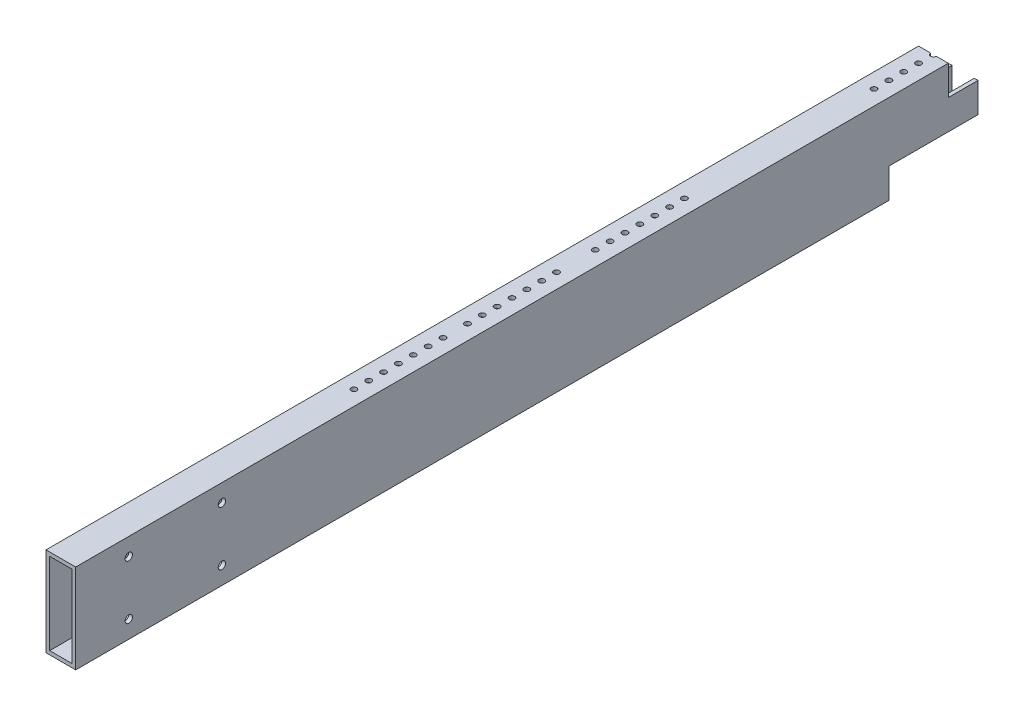
SolidWorks part; units mm, degrees
ref_plane "Front Plane" through (0, 0, 0) normal (0, 0, 1) x (1, 0, 0)
ref_plane "Top Plane" through (0, 0, 0) normal (0, 1, 0) x (1, 0, 0)
ref_plane "Right Plane" through (0, 0, 0) normal (1, 0, 0) x (0, 0, -1)
sketch "Sketch1" plane through (0, 0, 0) normal (0, 0, 1) x (1, 0, 0)
  line L1 (-12.7, -38.1) -> (12.7, -38.1)
  line L2 (-12.7, -38.1) -> (-12.7, 38.1)
  line L3 (-12.7, 38.1) -> (12.7, 38.1)
  line L4 (12.7, -38.1) -> (12.7, 38.1)
  line L5 (-12.7, -38.1) -> (12.7, 38.1) construction
  line L6 (-12.7, 38.1) -> (12.7, -38.1) construction
  point P0 (0, 0)
  dimension "D1" = 25.4
  dimension "D2" = 76.2
extrude "Boss-Extrude1" add sketch "Sketch1" along normal mid plane 771.398
shell "Shell1" thickness 3.175 removed face at (0, 0, -385.699) removed face at (0, 0, 385.699)
sketch "Sketch2" plane through (12.7, 0, 0) normal (1, 0, 0) x (0, 0, -1)
  line L1 (385.699, -38.1) -> (309.499, -38.1)
  line L2 (385.699, -38.1) -> (385.699, -12.7)
  line L3 (385.699, -12.7) -> (309.499, -12.7)
  line L4 (309.499, -38.1) -> (309.499, -12.7)
  dimension "D1" = 25.4
  dimension "D2" = 76.2
extrude "Cut-Extrude1" cut sketch "Sketch2" against normal through all
sketch "Sketch3" plane through (12.7, 0, 0) normal (1, 0, 0) x (0, 0, -1)
  line L1 (385.699, 38.1) -> (360.299, 38.1)
  line L2 (385.699, 38.1) -> (385.699, 12.7)
  line L3 (385.699, 12.7) -> (360.299, 12.7)
  line L4 (360.299, 38.1) -> (360.299, 12.7)
  dimension "D1" = 25.4
extrude "Cut-Extrude2" cut sketch "Sketch3" against normal through all
sketch "Sketch4" plane through (0, 38.1, 0) normal (0, 1, 0) x (1, 0, 0)
  line L0 (-12.7, 360.299) -> (12.7, 360.299) construction
  circle A0 centre (0, 147.3945) radius 2.3812
  circle A1 centre (0, 134.6945) radius 2.3812
  circle A2 centre (0, 121.9945) radius 2.3812
  circle A3 centre (0, 109.2945) radius 2.3812
  circle A4 centre (0, 96.5945) radius 2.3812
  circle A5 centre (0, 83.8945) radius 2.3812
  circle A6 centre (0, 71.1945) radius 2.3812
  circle A7 centre (0, 38.0987) radius 2.3812
  circle A8 centre (0, 25.3987) radius 2.3813
  circle A9 centre (0, 12.6987) radius 2.3813
  circle A10 centre (0, -0.0013) radius 2.3813
  circle A11 centre (0, -12.7013) radius 2.3812
  circle A12 centre (0, -25.4013) radius 2.3812
  circle A13 centre (0, -38.1013) radius 2.3812
  circle A15 centre (0, -58.9932) radius 2.3812
  circle A16 centre (0, -71.6932) radius 2.3812
  circle A17 centre (0, -84.3932) radius 2.3812
  circle A18 centre (0, -97.0932) radius 2.3812
  circle A19 centre (0, -109.7932) radius 2.3812
  circle A20 centre (0, -122.4932) radius 2.3812
  circle A21 centre (0, -135.1932) radius 2.3813
  point P33 (0, 360.299)
  dimension "D1" = 4.7625
  dimension "D3" = 12.7
  dimension "D4" = 12.7
  dimension "D5" = 12.7
  dimension "D6" = 12.7
  dimension "D7" = 12.7
  dimension "D8" = 12.7
  dimension "D9" = 322.2003
  dimension "D10" = 12.7
  dimension "D11" = 12.7
  dimension "D12" = 12.7
  dimension "D13" = 12.7
  dimension "D14" = 12.7
  dimension "D15" = 12.7
  dimension "D16" = 12.7
  dimension "D17" = 419.2922
  dimension "D18" = 12.7
  dimension "D19" = 12.7
  dimension "D20" = 12.7
  dimension "D21" = 12.7
  dimension "D22" = 12.7
  dimension "D2" = 212.9045
extrude "Cut-Extrude3" cut sketch "Sketch4" against normal through all
sketch "Sketch5" plane through (0, 38.1, 0) normal (0, 1, 0) x (1, 0, 0)
  line L0 (-12.7, 360.299) -> (12.7, 360.299) construction
  circle A0 centre (0, 360.299) radius 2.3813
  circle A1 centre (0, 347.599) radius 2.3813
  circle A2 centre (0, 334.899) radius 2.3813
  circle A3 centre (0, 322.199) radius 2.3813
  circle A4 centre (0, 309.499) radius 2.3813
  dimension "D1" = 4.7625
  dimension "D3" = 12.7
  dimension "D4" = 12.7
  dimension "D5" = 12.7
  dimension "D8" = 0
  dimension "D2" = 12.7
extrude "Cut-Extrude4" cut sketch "Sketch5" against normal up to next
sketch "Sketch6" plane through (0, -38.1, 0) normal (0, -1, 0) x (1, 0, 0)
  line L0 (-12.7, -309.499) -> (12.7, -309.499) construction
  circle A0 centre (0, -309.499) radius 2.3813
  circle A1 centre (0, -296.799) radius 2.3813
  circle A2 centre (0, -284.099) radius 2.3813
  circle A3 centre (0, -258.699) radius 2.3813
  circle A6 centre (0, -271.399) radius 2.3813
  dimension "D1" = 4.7625
  dimension "D2" = 12.7
  dimension "D3" = 12.7
  dimension "D4" = 12.7
  dimension "D5" = 12.7
  dimension "D6" = 0
extrude "Cut-Extrude5" cut sketch "Sketch6" against normal up to next
sketch3d "3DSketch1" [suppressed]
  line L0 (0, 34.925, -109.2945) -> (0, 38.1, -109.2945) construction
  line L1 (0, 34.925, 97.0932) -> (0, 38.1, 97.0932) construction
  point P0 (0, 38.1, -109.2945)
  point P1 (0, 0, 0)
  point P4 (0, 38.1, 97.0932)
sketch "Sketch11" plane through (12.7, 0, 0) normal (1, 0, 0) x (0, 0, -1)
  point P0 (-340.3244, 23.1254)
  point P1 (-260.7244, 23.1254)
  point P3 (-260.7244, -23.1)
  point P5 (-340.3244, -23.1)
hole_wizard "CBORE for M6 Hex Head Bolt1" positions "Sketch19" profile "Sketch18" counterbore size "M6" standard "Lanco STD" end condition through all
sketch "Sketch19" plane through (-12.7, 0, 0) normal (-1, 0, 0) x (0, 0, 1)
  point P0 (260.7244, 23.1254)
  point P3 (260.7244, -23.1)
  point P6 (340.3244, 23.1254)
  point P9 (340.3244, -23.1)
sketch "Sketch18" plane through (-12.7, 23.1254, 260.7244) normal (0, 1, 0) x (0, 0, 1)
  line L0 (0, 0) -> (0, 25.4)
  line L1 (0, 25.4) -> (3.15, 25.4)
  line L3 (3.15, 25.4) -> (3.15, 4)
  line L4 (3.15, 4) -> (7.2735, 4)
  line L5 (7.2735, 4) -> (7.2735, 0)
  line L7 (7.2735, 0) -> (0, 0)
  line L11 (0, -6.35) -> (0, 107.95) construction
  dimension "Thru Hole Dia." = 6.3
  dimension "Thru Hole Depth" = 25.4
  dimension "C'Bore Dia." = 14.547
  dimension "C'Bore Depth" = 4
